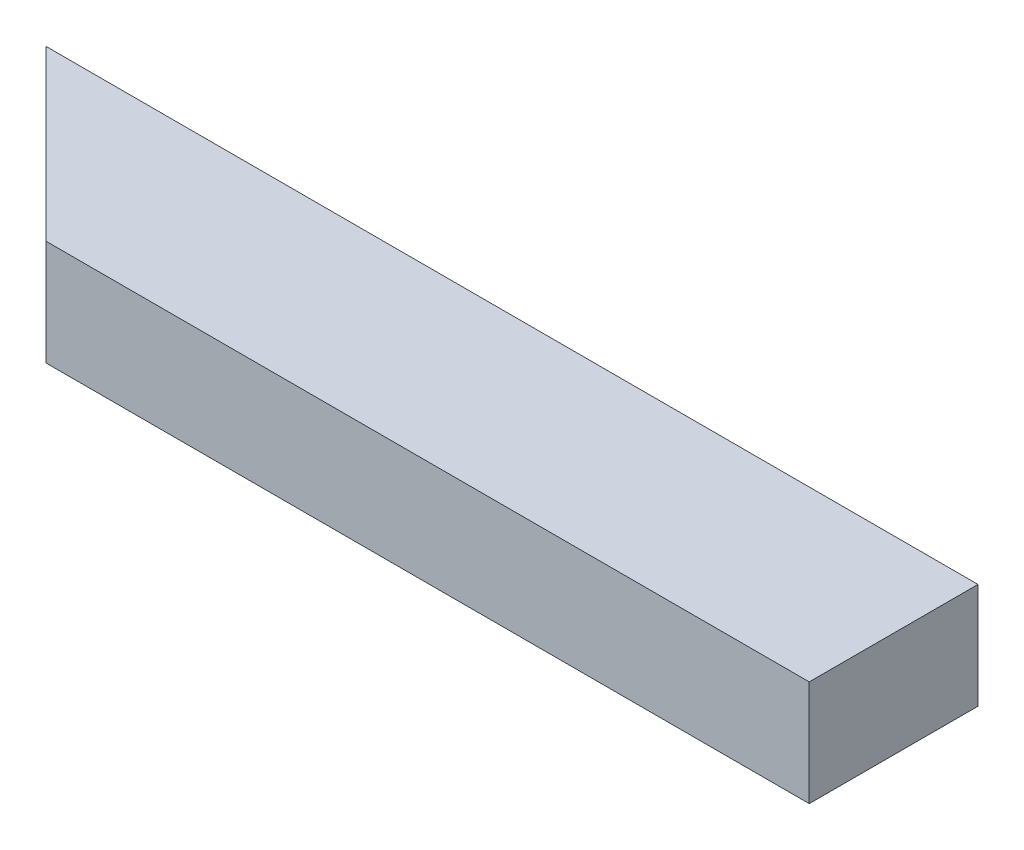
SolidWorks part; units mm, degrees
ref_plane "Front Plane" through (0, 0, 0) normal (0, 0, 1) x (1, 0, 0)
ref_plane "Top Plane" through (0, 0, 0) normal (0, 1, 0) x (1, 0, 0)
ref_plane "Right Plane" through (0, 0, 0) normal (1, 0, 0) x (0, 0, -1)
sketch "Sketch2" plane through (0, 0, 0) normal (0, 0, 1) x (1, 0, 0)
  line L0 (-244.7264, -11.1125) -> (-244.7264, 14.2875) construction
  line L1 (-216.6712, -11.1125) -> (-244.7264, -11.1125)
  line L2 (-216.6712, -11.1125) -> (-216.6712, -7.9375)
  line L3 (-216.6712, -7.9375) -> (-244.7264, -7.9375)
  line L4 (-244.7264, -11.1125) -> (-244.7264, -7.9375)
  dimension "D1" = 3.175
extrude "Boss-Extrude1" add sketch "Sketch2" along normal blind 5.08
chamfer "Chamfer1" distance 5.08 angle 45 1 edges at (-244.7264, -9.525, 5.08)
